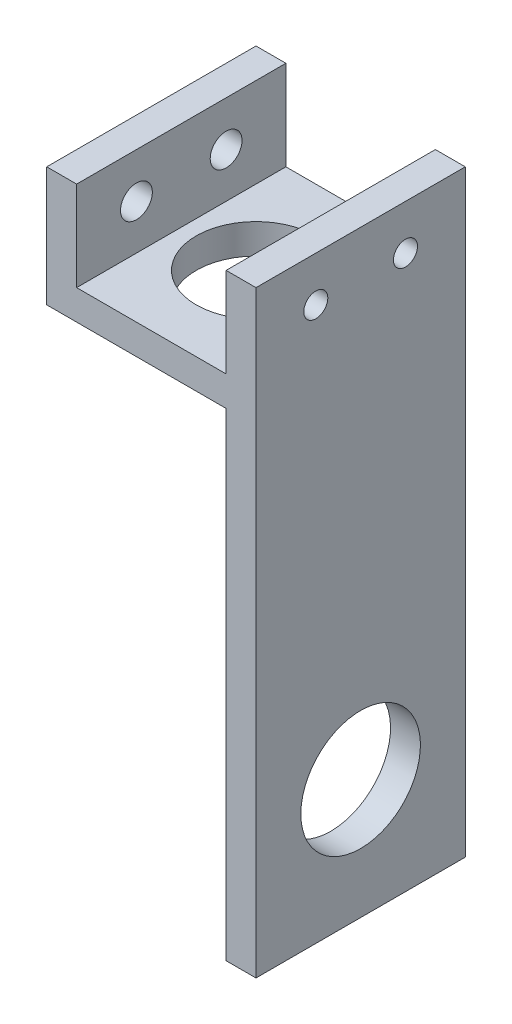
SolidWorks part; units mm, degrees
ref_plane "Front" through (0, 0, 0) normal (0, 0, 1) x (1, 0, 0)
ref_plane "Top" through (0, 0, 0) normal (0, 1, 0) x (1, 0, 0)
ref_plane "Right" through (0, 0, 0) normal (1, 0, 0) x (0, 0, -1)
sketch "Sketch1" plane through (0, 0, 0) normal (0, 0, 1) x (1, 0, 0)
  line L0 (0, 0) -> (6.35, 0)
  line L1 (6.35, 0) -> (6.35, 127)
  line L2 (6.35, 127) -> (0, 127)
  line L3 (0, 127) -> (0, 107.95)
  line L4 (0, 107.95) -> (-31.75, 107.95)
  line L5 (-31.75, 107.95) -> (-31.75, 127)
  line L6 (-31.75, 127) -> (-38.1, 127)
  line L7 (-38.1, 127) -> (-38.1, 101.6)
  line L8 (-38.1, 101.6) -> (0, 101.6)
  line L9 (0, 101.6) -> (0, 0)
  point P3 (3.175, 0)
  dimension "D1" = 6.35
  dimension "D2" = 101.6
  dimension "D3" = 31.75
  dimension "D4" = 6.35
  dimension "D5" = 6.35
  dimension "D6" = 19.05
  dimension "D7" = 19.05
  dimension "D8" = 6.35
extrude "Boss-Extrude1" add sketch "Sketch1" along normal blind 44.45
sketch "Sketch2" plane through (0, 0, 0) normal (-1, 0, 0) x (0, 0, 1)
  line L0 (44.45, 0) -> (0, 0) construction
  line L1 (44.45, 101.6) -> (44.45, 0) construction
  circle A0 centre (22.225, 25.4) radius 12.7
  dimension "D3" = 25.4
  dimension "D1" = 25.4
  dimension "D2" = 22.225
extrude "Cut-Extrude1" cut sketch "Sketch2" against normal blind 44.45
hole_wizard "1/4-20 Tapped Hole1" positions "Sketch3" profile "Sketch4" tap size "1/4-20" standard "ANSI Inch" end condition through all
sketch "Sketch3" plane through (0, 0, 0) normal (-1, 0, 0) x (0, 0, 1)
  line L2 (44.45, 127) -> (0, 127) construction
  line L3 (0, 127) -> (0, 107.95) construction
  point P0 (12.7, 117.475)
  point P2 (31.75, 117.475)
  point P25 (31.6214, 119.685)
  dimension "D1" = 19.05
  dimension "D2" = 9.525
  dimension "D3" = 12.7
sketch "Sketch4" plane through (0, 117.475, 12.7) normal (0, 1, 0) x (0, 0, 1)
  line L0 (0, 0) -> (0, 6.35)
  line L1 (0, 6.35) -> (2.5527, 6.35)
  line L2 (2.5527, 6.35) -> (2.5527, 0)
  line L5 (2.5527, 0) -> (0, 0)
  line L11 (0, -6.35) -> (0, 107.95) construction
  dimension "Thru Tap Drill Dia." = 5.1054
  dimension "Thru Tap Drill Depth" = 6.35
cosmetic thread "Hole Thread1" parameters "D2"=6.35
cosmetic thread "Hole Thread2" parameters "D2"=6.35
sketch "Sketch5" plane through (-38.1, 0, 0) normal (-1, 0, 0) x (0, 0, 1)
  line L0 (44.45, 127) -> (0, 127) construction
  line L1 (44.45, 127) -> (44.45, 101.6) construction
  circle A0 centre (12.7, 117.475) radius 3.3782
  circle A1 centre (31.75, 117.475) radius 3.3782
  dimension "D4" = 6.7564
  dimension "D1" = 19.05
  dimension "D2" = 9.525
  dimension "D3" = 12.7
extrude "Cut-Extrude2" cut sketch "Sketch5" against normal blind 8.89
sketch "Sketch6" plane through (0, 107.95, 0) normal (0, 1, 0) x (1, 0, 0)
  line L0 (6.35, -44.45) -> (0, -44.45) construction
  line L2 (0, -44.45) -> (0, 0) construction
  circle A0 centre (-15.875, -22.225) radius 12.7
  dimension "D1" = 25.4
  dimension "D2" = 22.225
  dimension "D3" = 15.875
extrude "Cut-Extrude3" cut sketch "Sketch6" against normal blind 8.89
